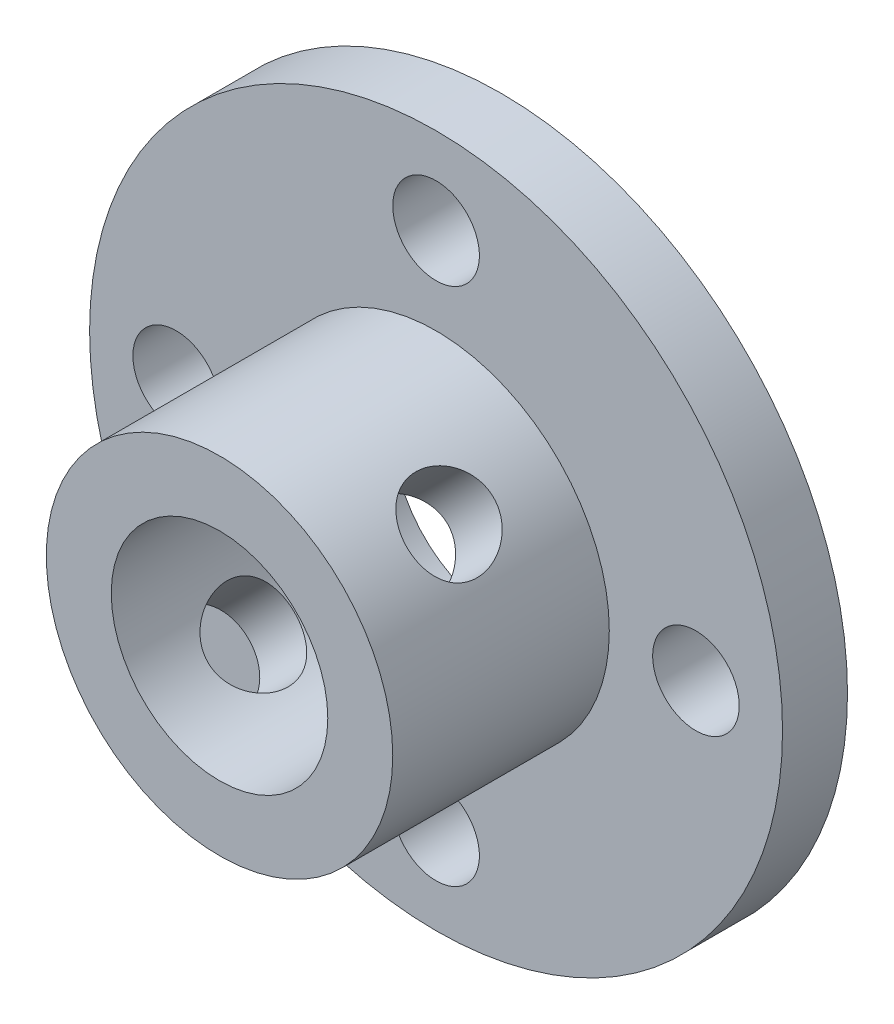
SolidWorks part; units mm, degrees
ref_plane "前视基准面" through (0, 0, 0) normal (0, 0, 1) x (1, 0, 0)
ref_plane "上视基准面" through (0, 0, 0) normal (0, 1, 0) x (1, 0, 0)
ref_plane "右视基准面" through (0, 0, 0) normal (1, 0, 0) x (0, 0, -1)
sketch "草图1" plane through (0, 0, 0) normal (0, 0, 1) x (1, 0, 0)
  circle A0 centre (0, 0) radius 8
  circle A1 centre (0, 0) radius 5
  dimension "D1" = 16
  dimension "D2" = 10
extrude "凸台-拉伸1" add sketch "草图1" along normal blind 10
sketch "草图2" plane through (0, 0, 0) normal (0, 0, -1) x (-1, 0, 0)
  circle A0 centre (0, 0) radius 5
  circle A1 centre (0, 0) radius 16
  circle A2 centre (0, 0) radius 12 construction
  circle A3 centre (-12, 0) radius 2
  circle A4 centre (0, 12) radius 2
  circle A5 centre (12, 0) radius 2
  circle A6 centre (0, -12) radius 2
  dimension "D1" = 32
  dimension "D2" = 24
  dimension "D3" = 4
  dimension "D4" = 4
extrude "凸台-拉伸2" add sketch "草图2" along normal blind 3
ref_axis "基准轴1" through (0, 0, 10) along (0, 0, -1)
ref_plane "基准面1" through (0, 0, 0) normal (0.7071, 0.7071, 0) x (0, 0, -1)
sketch "草图3" plane through (0, 0, 0) normal (0.7071, 0.7071, 0) x (0, 0, -1)
  line L0 (-10, 0) -> (0, 0) construction
  line L2 (-10, 8) -> (-10, -8) construction
  circle A0 centre (-5, 0) radius 2
  dimension "D1" = 4
extrude "切除-拉伸1" cut sketch "草图3" against normal blind 10 and the other way blind 10
